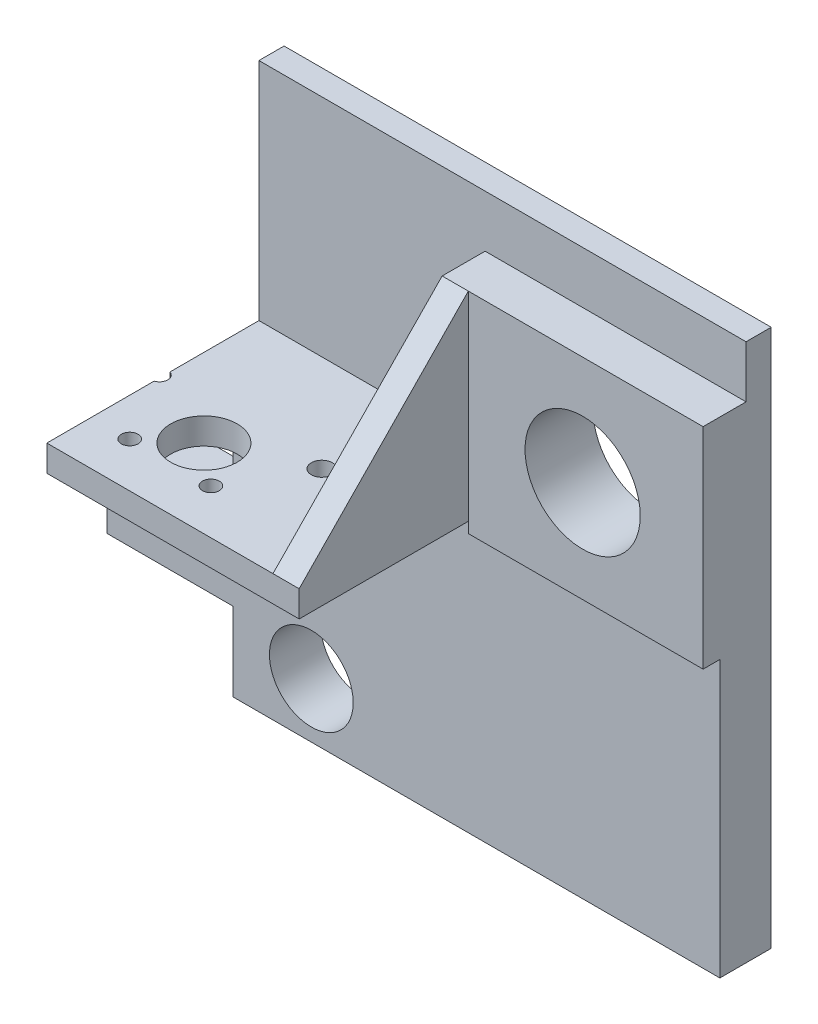
SolidWorks part; units mm, degrees
material "ABS"
ref_plane "Front Plane" through (0, 0, 0) normal (0, 0, 1) x (1, 0, 0)
ref_plane "Top Plane" through (0, 0, 0) normal (0, 1, 0) x (1, 0, 0)
ref_plane "Right Plane" through (0, 0, 0) normal (1, 0, 0) x (0, 0, -1)
sketch "Sketch1" plane through (0, 0, 0) normal (0, 0, 1) x (1, 0, 0)
  line L0 (-24, 15) -> (0, 15)
  line L1 (0, 15) -> (0, 0)
  line L2 (0, 0) -> (93, 0)
  line L3 (93, 0) -> (93, 102.7)
  line L4 (93, 102.7) -> (0, 102.7)
  line L5 (0, 102.7) -> (0, 30)
  line L6 (0, 30) -> (-24, 30)
  line L7 (-24, 30) -> (-24, 15)
  circle A0 centre (15, 10.5) radius 8
  circle A1 centre (70, 72) radius 11
  circle A2 centre (15, 10.5) radius 11
  dimension "D1" = 15
  dimension "D10" = 16
  dimension "D11" = 22
  dimension "D12" = 22
  dimension "D2" = 24
  dimension "D3" = 72.7
  dimension "D4" = 15
  dimension "D5" = 15
  dimension "D6" = 10.5
  dimension "D7" = 82.5061
  dimension "D8" = 72
  dimension "D9" = 93
extrude "Boss-Extrude1" add sketch "Sketch1" along normal blind 4.8 contours A2 L2 L3 L4 L5 L6 L7 L0 L1 A1 | L2 A2 A0 region at (44.5238, 51.0418, 0) region at (8.6656, 19.1141, 0)
sketch "Sketch2" plane through (0, 0, 4.8) normal (0, 0, 1) x (1, 0, 0)
  line L0 (93, 0) -> (93, 102.7) construction
  line L1 (48.1786, 92.7632) -> (93, 92.7632)
  line L2 (48.1786, 92.7632) -> (48.1786, 52.666)
  line L3 (48.1786, 52.666) -> (93, 52.666)
  line L4 (93, 92.7632) -> (93, 52.666)
  line L5 (48.1786, 92.7632) -> (93, 52.666) construction
  line L6 (48.1786, 52.666) -> (93, 92.7632) construction
  circle A0 centre (70, 72) radius 11
  circle A1 centre (70, 72) radius 4.15
  point P8 (70.5893, 72.7146)
  line M4 (93, 0) -> (93, 102.7)
  circle M10 centre (70, 72) radius 11
  dimension "D1" = 22
  dimension "D2" = 8.3
extrude "Boss-Extrude2" add sketch "Sketch2" along normal blind 8.2 contours L2 L3 L1 M4 M10 region at (70.5893, 92.1618, 4.8)
sketch "Sketch3" plane through (0, 0, 4.8) normal (0, 0, 1) x (1, 0, 0)
  line L1 (-24, 15) -> (0, 15)
  line L2 (-24, 15) -> (-24, 30)
  line L3 (-24, 30) -> (0, 30)
  line L4 (0, 15) -> (0, 30)
  line L5 (-24, 15) -> (0, 30) construction
  line L6 (-24, 30) -> (0, 15) construction
  line L7 (0, 0) -> (93, 0)
  line L8 (0, 0) -> (0, 52.666)
  line L9 (0, 52.666) -> (93, 52.666)
  line L10 (93, 0) -> (93, 52.666)
  line L11 (0, 0) -> (93, 52.666) construction
  line L12 (0, 52.666) -> (93, 0) construction
  circle A0 centre (15, 10.5) radius 8
  point P4 (-12, 22.5)
  point P11 (46.5, 26.333)
  circle M1 centre (15, 10.5) radius 8
  line M6 (0, 102.7) -> (0, 30)
  line M7 (0, 30) -> (-24, 30)
  line M8 (-24, 30) -> (-24, 15)
  line M9 (-24, 15) -> (0, 15)
  line M10 (0, 15) -> (0, 0)
  line M11 (0, 0) -> (93, 0)
  line M12 (93, 0) -> (93, 52.666)
  line M13 (93, 52.666) -> (48.1786, 52.666)
extrude "Boss-Extrude3" add sketch "Sketch3" along normal blind 5 contours L4 M9 M7 M8 | L9 L4 M6 M10 M11 M12 M13 M1 region at (-12, 22.5, 4.8) region at (47.8484, 27.0108, 4.8)
sketch "Sketch4" plane through (0, 59.701, 0) normal (0, -1, 0) x (1, 0, 0)
  line L0 (0, 9.8) -> (0, 4.8) construction
  line L1 (0, 4.8) -> (48.1786, 4.8)
  line L2 (0, 4.8) -> (0, 45.3)
  line L3 (0, 45.3) -> (48.1786, 45.3)
  line L4 (48.1786, 4.8) -> (48.1786, 45.3)
  line L5 (0, 4.8) -> (48.1786, 45.3) construction
  line L6 (0, 45.3) -> (48.1786, 4.8) construction
  line L7 (0, 4.8) -> (48.1786, 4.8) construction
  line L8 (48.1786, 13) -> (48.1786, 9.8) construction
  line L9 (0, 0) -> (93, 0) construction
  line L10 (0, 45.3) -> (-5, 45.3)
  line L11 (0, 45.3) -> (0, 0)
  line L12 (0, 0) -> (-5, 0)
  line L13 (-5, 45.3) -> (-5, 0)
  line L14 (0, 45.3) -> (-5, 0) construction
  line L15 (0, 0) -> (-5, 45.3) construction
  circle A0 centre (15, 30.3) radius 6.35
  circle A1 centre (15, 23.3) radius 18.5
  circle A3 centre (30.5, 23.3) radius 2
  circle A4 centre (22.75, 9.8766) radius 2
  circle A5 centre (7.25, 9.8766) radius 2
  point P10 (24.0893, 25.05)
  point P30 (-2.5, 22.65)
  arc M5 (6.0925, 30.9329) -> (23.9075, 30.9329) centre (15, 30.3) ccw
  arc M7 (24.2388, 31.0672) -> (5.7612, 31.0672) centre (15, 23.3) cw
  circle M9 centre (22.75, 9.8766) radius 1.6
  circle M10 centre (7.25, 9.8766) radius 1.6
  circle M11 centre (-0.5, 23.3) radius 1.6
  circle M12 centre (7.25, 36.7234) radius 1.6
  circle M13 centre (22.75, 36.7234) radius 1.6
  circle M15 centre (28.4234, 31.05) radius 2.1
  circle M16 centre (1.5766, 31.05) radius 2.1
  circle M17 centre (15, 7.8) radius 2.1
  circle M19 centre (15, 23.3) radius 18.5
  dimension "D1" = 12.7
  dimension "D2" = 15
  dimension "D3" = 4
  dimension "D4" = 4
  dimension "D5" = 4
  dimension "D6" = 5
  dimension "D7" = 0
extrude "Boss-Extrude4" add sketch "Sketch4" along normal blind 5 contours L1 L4 L3 M19 | A0 L3 L2 A5 A4 A3 M12 M19 M16 M11 M13 M17 M15 M5 M7 | M5 M7 | M17 | A4 M9 | M9 | M10 | A5 M10 | M15 | L2 M16 | L2 L1 M19 region at (3.5769, 59.701, 6.9879) region at (34.3513, 59.701, 27.7532) region at (15.8399, 59.701, 22.3532) region at (1.715, 59.701, 31.05) region at (20.8066, 59.701, 9.8766) region at (5.3066, 59.701, 9.8766) region at (22.75, 59.701, 9.8766) region at (7.25, 59.701, 9.8766) region at (28.4234, 59.701, 31.05) region at (15, 59.701, 7.8)
sketch "Sketch5" plane through (48.1786, 0, 0) normal (1, 0, 0) x (0, 0, -1)
  line L0 (-45.3, 59.701) -> (-13, 92.7632)
  line L1 (-13, 92.7632) -> (-4.8, 92.7632)
  line L2 (-4.8, 92.7632) -> (-4.8, 54.701)
  line L3 (-4.8, 54.701) -> (-45.3, 54.701)
  line L4 (-45.3, 54.701) -> (-45.3, 59.701)
extrude "Boss-Extrude5" add sketch "Sketch5" against normal blind 5
